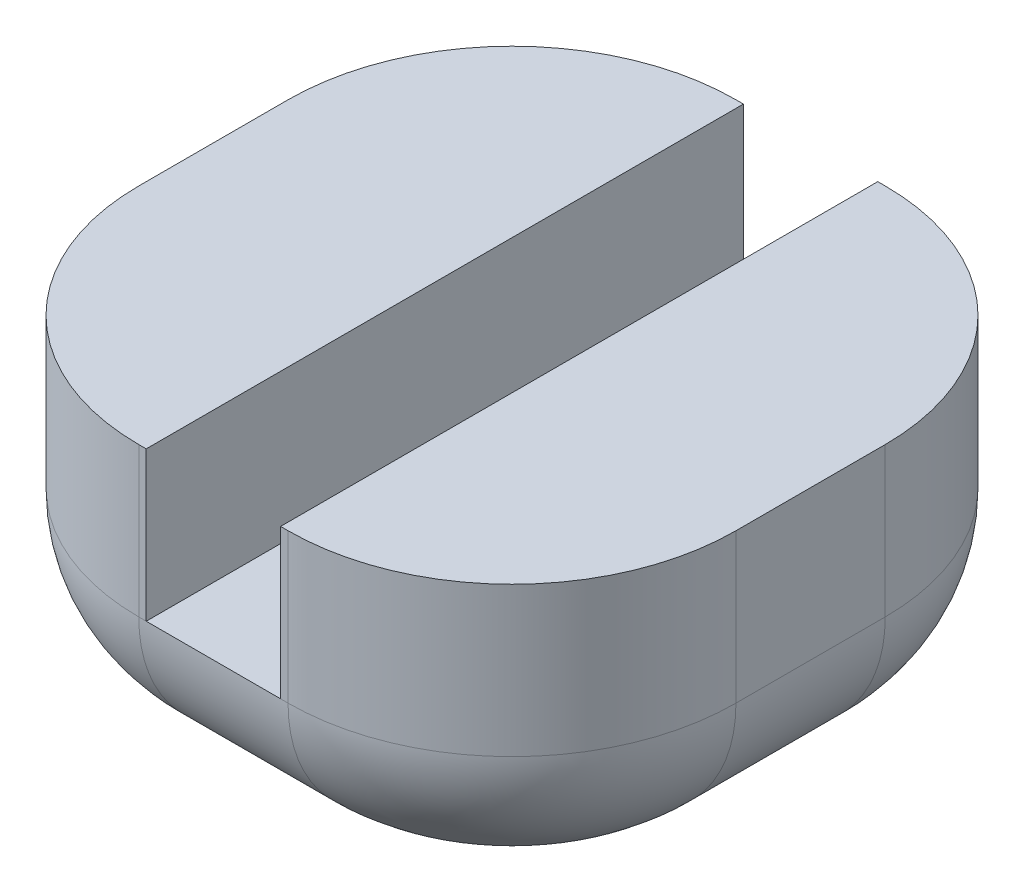
SolidWorks part; units mm, degrees
ref_plane "Front" through (0, 0, 0) normal (0, 0, 1) x (1, 0, 0)
ref_plane "Top" through (0, 0, 0) normal (0, 1, 0) x (1, 0, 0)
ref_plane "Right" through (0, 0, 0) normal (1, 0, 0) x (0, 0, -1)
sketch "草图1" plane through (0, 0, 0) normal (0, 1, 0) x (1, 0, 0)
  line L1 (2, -2) -> (-2, -2)
  line L2 (2, -2) -> (2, 2)
  line L3 (2, 2) -> (-2, 2)
  line L4 (-2, -2) -> (-2, 2)
  line L5 (2, -2) -> (-2, 2) construction
  line L6 (2, 2) -> (-2, -2) construction
  point P0 (0, 0)
  dimension "D1" = 4
  dimension "D2" = 4
extrude "凸台-拉伸1" add sketch "草图1" along normal blind 2
fillet "圆角1" radius 1.5 4 edges at (-2, 1, -2) (2, 1, -2) (2, 1, 2) (-2, 1, 2)
sketch "草图2" plane through (0, 2, 0) normal (0, 1, 0) x (1, 0, 0)
  circle A0 centre (0, 0) radius 0.45
  dimension "D1" = 0.9
extrude "切除-拉伸1" cut sketch "草图2" against normal through all
sketch "草图3" plane through (0, 2, 0) normal (0, 1, 0) x (1, 0, 0)
  line L0 (0.5, 2) -> (-0.5, 2) construction
  line L1 (0.45, -2) -> (-0.45, -2)
  line L2 (0.45, -2) -> (0.45, 2)
  line L3 (0.45, 2) -> (-0.45, 2)
  line L4 (-0.45, -2) -> (-0.45, 2)
  line L5 (0.45, -2) -> (-0.45, 2) construction
  line L6 (0.45, 2) -> (-0.45, -2) construction
  circle A0 centre (0, 0) radius 0.45 construction
  point P0 (0, 0)
extrude "切除-拉伸2" cut sketch "草图3" against normal blind 1
fillet "圆角3" radius 1 8 edges at (1.5607, 0, -1.5607) (2, 0, 0) (1.5607, 0, 1.5607) (0, 0, 2) (-1.5607, 0, 1.5607) (-2, 0, 0) (-1.5607, 0, -1.5607) (0, 0, -2)
